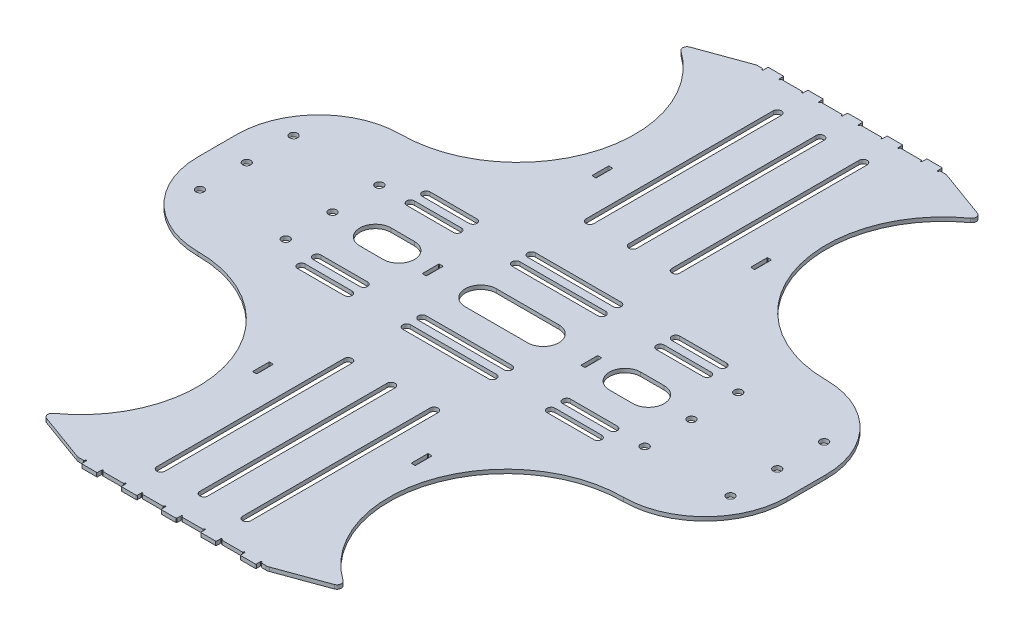
SolidWorks part; units mm, degrees
material "6061-T6 (SS)"
ref_plane "Front Plane" through (0, 0, 0) normal (0, 0, 1) x (1, 0, 0)
ref_plane "Top Plane" through (0, 0, 0) normal (0, 1, 0) x (1, 0, 0)
ref_plane "Right Plane" through (0, 0, 0) normal (1, 0, 0) x (0, 0, -1)
sketch "Sketch1" plane through (0, 0, 0) normal (0, 1, 0) x (1, 0, 0)
  line L0 (0, 0.6294) -> (0, -0.6294) construction
  line L1 (11.2708, 0) -> (-11.2708, 0) construction
  line L2 (76.108, 276.225) -> (-76.108, 276.225)
  line L3 (-78.2798, 275.842) -> (-117.0656, 261.7252)
  line L4 (-173.1053, 82.55) -> (-251.6278, 82.55) construction
  line L5 (239.7803, 15.875) -> (239.7803, -15.875)
  line L6 (78.2798, 275.842) -> (117.0656, 261.7252)
  line L7 (78.2798, -275.842) -> (117.0656, -261.7252)
  line L8 (-78.2798, -275.842) -> (-117.0656, -261.7252)
  line L9 (76.108, -276.225) -> (-76.108, -276.225)
  line L10 (-215.9, -92.7049) -> (-215.9, 92.7049) construction
  line L11 (215.9, -92.7049) -> (215.9, 92.7049) construction
  line L12 (-239.7803, 15.875) -> (-239.7803, -15.875)
  arc A0 (-76.108, 276.225) -> (-78.2798, 275.842) centre (-76.108, 269.875) ccw
  arc A1 (-117.0656, 261.7252) -> (-117.9169, 255.4325) centre (-115.8391, 258.3553) ccw
  arc A2 (-117.9169, 255.4325) -> (-173.1053, 82.55) centre (-173.1053, 177.8) cw
  arc A3 (-173.1053, 82.55) -> (-239.7803, 15.875) centre (-173.1053, 15.875) ccw
  arc A4 (173.1053, 82.55) -> (239.7803, 15.875) centre (173.1053, 15.875) cw
  arc A5 (117.9169, 255.4325) -> (173.1053, 82.55) centre (173.1053, 177.8) ccw
  arc A6 (117.0656, 261.7252) -> (117.9169, 255.4325) centre (115.8391, 258.3553) cw
  arc A7 (76.108, 276.225) -> (78.2798, 275.842) centre (76.108, 269.875) cw
  arc A8 (76.108, -276.225) -> (78.2798, -275.842) centre (76.108, -269.875) ccw
  arc A9 (117.0656, -261.7252) -> (117.9169, -255.4325) centre (115.8391, -258.3553) ccw
  arc A10 (117.9169, -255.4325) -> (173.1053, -82.55) centre (173.1053, -177.8) cw
  arc A11 (173.1053, -82.55) -> (239.7803, -15.875) centre (173.1053, -15.875) ccw
  arc A12 (-173.1053, -82.55) -> (-239.7803, -15.875) centre (-173.1053, -15.875) cw
  arc A13 (-117.9169, -255.4325) -> (-173.1053, -82.55) centre (-173.1053, -177.8) ccw
  arc A14 (-117.0656, -261.7252) -> (-117.9169, -255.4325) centre (-115.8391, -258.3553) cw
  arc A15 (-76.108, -276.225) -> (-78.2798, -275.842) centre (-76.108, -269.875) cw
  circle A16 centre (-215.9, 0) radius 3.2639
  circle A17 centre (-215.9, 38.1) radius 3.2639
  circle A18 centre (-215.9, -38.1) radius 3.2639
  circle A19 centre (215.9, -38.1) radius 3.2639
  circle A20 centre (215.9, 0) radius 3.2639
  circle A21 centre (215.9, 38.1) radius 3.2639
  circle A22 centre (-146.05, 0) radius 3.2639
  circle A23 centre (-146.05, 38.1) radius 3.2639
  circle A24 centre (-146.05, -38.1) radius 3.2639
  circle A25 centre (146.05, -38.1) radius 3.2639
  circle A26 centre (146.05, 38.1) radius 3.2639
  circle A27 centre (146.05, 0) radius 3.2639
  point P3 (77.2277, 276.225)
  point P10 (-77.2277, 276.225)
  point P17 (0, -276.225)
  point P28 (-239.7803, 0)
  point P29 (0, 276.225)
  point P50 (239.7803, 0)
  point P51 (-77.2277, -276.225)
  point P52 (77.2277, -276.225)
  dimension "D4" = 6.35
  dimension "D6" = 95.25
  dimension "D9" = 66.675
  dimension "D10" = 6.5278
  dimension "D13" = 38.1
  dimension "D2" = 20
  dimension "D3" = 41.275
  dimension "D5" = 6.35
  dimension "D7" = 276.225
  dimension "D8" = 31.75
  dimension "D11" = 76.108
  dimension "D12" = 431.8
  dimension "D15" = 69.85
  dimension "D14" = 2
base flange "Base-Flange1" sketch "Sketch1" thickness 3.175 reverse thickness direction no parameters "D1"=6.35
ref_plane "True MidPlane" through (0, -1.5875, 0) normal (0, 1, 0) x (1, 0, 0)
sketch "Sketch6" plane through (0, 0, -276.225) normal (0, 0, -1) x (-1, 0, 0)
  line L0 (-76.108, 0) -> (76.108, 0) construction
  line L1 (-6.35, 0) -> (6.35, 0)
  line L2 (-6.35, 0) -> (-6.35, -3.175)
  line L3 (-6.35, -3.175) -> (6.35, -3.175)
  line L4 (6.35, 0) -> (6.35, -3.175)
  line L5 (-6.35, 0) -> (6.35, -3.175) construction
  line L6 (-6.35, -3.175) -> (6.35, 0) construction
  line L7 (-76.108, -3.175) -> (76.108, -3.175) construction
  line L8 (25.9397, 0) -> (38.6397, 0)
  line L9 (25.9397, 0) -> (25.9397, -3.175)
  line L10 (25.9397, -3.175) -> (38.6397, -3.175)
  line L11 (38.6397, 0) -> (38.6397, -3.175)
  line L12 (25.9397, 0) -> (38.6397, -3.175) construction
  line L13 (25.9397, -3.175) -> (38.6397, 0) construction
  line L14 (58.2295, 0) -> (70.9295, 0)
  line L15 (58.2295, 0) -> (58.2295, -3.175)
  line L16 (58.2295, -3.175) -> (70.9295, -3.175)
  line L17 (70.9295, 0) -> (70.9295, -3.175)
  line L18 (58.2295, 0) -> (70.9295, -3.175) construction
  line L19 (58.2295, -3.175) -> (70.9295, 0) construction
  line L20 (0, -1.5875) -> (0, 0) construction
  line L21 (-58.2295, -3.175) -> (-70.9295, 0) construction
  line L22 (-58.2295, 0) -> (-70.9295, -3.175) construction
  line L23 (-25.9397, -3.175) -> (-38.6397, 0) construction
  line L24 (-25.9397, 0) -> (-38.6397, -3.175) construction
  line L25 (-70.9295, 0) -> (-70.9295, -3.175)
  line L26 (-58.2295, -3.175) -> (-70.9295, -3.175)
  line L27 (-58.2295, 0) -> (-58.2295, -3.175)
  line L28 (-58.2295, 0) -> (-70.9295, 0)
  line L29 (-38.6397, 0) -> (-38.6397, -3.175)
  line L30 (-25.9397, -3.175) -> (-38.6397, -3.175)
  line L31 (-25.9397, 0) -> (-25.9397, -3.175)
  line L32 (-25.9397, 0) -> (-38.6397, 0)
  point P0 (0, -1.5875)
  point P11 (32.2897, -1.5875)
  point P16 (64.5795, -1.5875)
  point P30 (-64.5795, -1.5875)
  point P31 (-32.2897, -1.5875)
  dimension "D1" = 12.7
  dimension "D3" = 32.2897
  dimension "D2" = 3
extrude "Welding Tabs" add sketch "Sketch6" along normal blind 3.175
sketch "Sketch7" plane through (0, 0, 0) normal (0, 1, 0) x (1, 0, 0)
  line L0 (-71.9455, 276.225) -> (-71.9455, 275.59)
  line L1 (-70.9295, 276.225) -> (-76.108, 276.225) construction
  line L2 (-70.9295, 276.225) -> (-70.9295, 275.59)
  line L3 (-71.9455, 276.225) -> (-70.9295, 276.225)
  line L4 (-64.5795, 279.4) -> (-64.5795, 276.225) construction
  line L5 (-70.9295, 279.4) -> (-58.2295, 279.4) construction
  line L6 (-57.2135, 276.225) -> (-58.2295, 276.225)
  line L7 (-58.2295, 276.225) -> (-58.2295, 275.59)
  line L8 (-57.2135, 276.225) -> (-57.2135, 275.59)
  line L9 (-39.6557, 276.225) -> (-39.6557, 275.59)
  line L10 (-38.6397, 276.225) -> (-38.6397, 275.59)
  line L11 (-39.6557, 276.225) -> (-38.6397, 276.225)
  line L12 (-24.9238, 276.225) -> (-25.9398, 276.225)
  line L13 (-25.9398, 276.225) -> (-25.9398, 275.59)
  line L14 (-24.9238, 276.225) -> (-24.9238, 275.59)
  line L15 (-7.366, 276.225) -> (-7.366, 275.59)
  line L16 (-6.35, 276.225) -> (-6.35, 275.59)
  line L17 (-7.366, 276.225) -> (-6.35, 276.225)
  line L18 (7.366, 276.225) -> (6.35, 276.225)
  line L19 (6.35, 276.225) -> (6.35, 275.59)
  line L20 (7.366, 276.225) -> (7.366, 275.59)
  line L21 (24.9237, 276.225) -> (24.9237, 275.59)
  line L22 (25.9397, 276.225) -> (25.9397, 275.59)
  line L23 (24.9237, 276.225) -> (25.9397, 276.225)
  line L24 (39.6557, 276.225) -> (38.6397, 276.225)
  line L25 (38.6397, 276.225) -> (38.6397, 275.59)
  line L26 (39.6557, 276.225) -> (39.6557, 275.59)
  line L27 (57.2135, 276.225) -> (57.2135, 275.59)
  line L28 (58.2295, 276.225) -> (58.2295, 275.59)
  line L29 (57.2135, 276.225) -> (58.2295, 276.225)
  line L30 (71.9455, 276.225) -> (70.9295, 276.225)
  line L31 (70.9295, 276.225) -> (70.9295, 275.59)
  line L32 (71.9455, 276.225) -> (71.9455, 275.59)
  line L33 (-38.6397, 279.4) -> (-38.6397, 276.225) construction
  line L34 (-25.9397, 279.4) -> (-25.9397, 276.225) construction
  line L37 (6.35, 279.4) -> (6.35, 276.225) construction
  line L38 (-6.35, 279.4) -> (-6.35, 276.225) construction
  arc A0 (-71.9455, 275.59) -> (-70.9295, 275.59) centre (-71.4375, 275.59) ccw
  arc A1 (-57.2135, 275.59) -> (-58.2295, 275.59) centre (-57.7215, 275.59) cw
  arc A2 (-39.6557, 275.59) -> (-38.6397, 275.59) centre (-39.1478, 275.59) ccw
  arc A3 (-24.9238, 275.59) -> (-25.9398, 275.59) centre (-25.4318, 275.59) cw
  arc A4 (-7.366, 275.59) -> (-6.35, 275.59) centre (-6.858, 275.59) ccw
  arc A5 (7.366, 275.59) -> (6.35, 275.59) centre (6.858, 275.59) cw
  arc A6 (24.9237, 275.59) -> (25.9397, 275.59) centre (25.4317, 275.59) ccw
  arc A7 (39.6557, 275.59) -> (38.6397, 275.59) centre (39.1477, 275.59) cw
  arc A8 (57.2135, 275.59) -> (58.2295, 275.59) centre (57.7215, 275.59) ccw
  arc A9 (71.9455, 275.59) -> (70.9295, 275.59) centre (71.4375, 275.59) cw
  dimension "D2" = 0.508
  dimension "D1" = 0.635
  dimension "D3" = 5
extrude "Tab Reliefs" cut sketch "Sketch7" against normal through all normal cut yes
mirror "Mirror Tabs" about plane through (0, 0, 0) normal (0, 0, 1) of "Tab Reliefs", "Welding Tabs"
fillet "Fillets for Cutter" radius 0.508 40 edges at (57.2135, -1.5875, -276.225) (71.9455, -1.5875, -276.225) (39.6557, -1.5875, -276.225) (24.9237, -1.5875, -276.225) (7.366, -1.5875, -276.225) (-7.366, -1.5875, -276.225) (-24.9238, -1.5875, -276.225) (-39.6557, -1.5875, -276.225) (-57.2135, -1.5875, -276.225) (-71.9455, -1.5875, -276.225) (57.2135, -1.5875, 276.225) (39.6557, -1.5875, 276.225) (24.9237, -1.5875, 276.225) (7.366, -1.5875, 276.225) (-7.366, -1.5875, 276.225) (-24.9238, -1.5875, 276.225) (-39.6557, -1.5875, 276.225) (-57.2135, -1.5875, 276.225) (-71.9455, -1.5875, 276.225) (70.9295, -1.5875, -279.4) (58.2295, -1.5875, -279.4) (38.6397, -1.5875, -279.4) (25.9397, -1.5875, -279.4) (6.35, -1.5875, -279.4) (-6.35, -1.5875, -279.4) (-25.9397, -1.5875, -279.4) (-38.6397, -1.5875, -279.4) (-58.2295, -1.5875, -279.4) (-70.9295, -1.5875, -279.4) (71.9455, -1.5875, 276.225) (70.9295, -1.5875, 279.4) (58.2295, -1.5875, 279.4) (38.6397, -1.5875, 279.4) (25.9397, -1.5875, 279.4) (6.35, -1.5875, 279.4) (-6.35, -1.5875, 279.4) (-25.9397, -1.5875, 279.4) (-38.6397, -1.5875, 279.4) (-58.2295, -1.5875, 279.4) (-70.9295, -1.5875, 279.4)
sketch "Sketch8" plane through (0, 0, 0) normal (0, 1, 0) x (1, 0, 0)
  line L0 (0, -78.4488) -> (0, 78.4488) construction
  line L1 (-65.7479, 6.858) -> (-63.4111, 6.858)
  line L2 (-65.7479, 144.9705) -> (-63.4111, 144.9705)
  line L3 (-66.2559, 144.4625) -> (-66.2559, 131.7625)
  line L4 (-65.7479, 131.2545) -> (-63.4111, 131.2545)
  line L5 (-62.9031, 144.4625) -> (-62.9031, 131.7625)
  line L6 (-66.2559, 144.9705) -> (-62.9031, 131.2545) construction
  line L7 (-66.2559, 131.2545) -> (-62.9031, 144.9705) construction
  line L8 (-66.2559, 6.35) -> (-66.2559, -6.35)
  line L9 (-65.7479, -6.858) -> (-63.4111, -6.858)
  line L10 (-62.9031, 6.35) -> (-62.9031, -6.35)
  line L11 (-66.2559, 6.858) -> (-62.9031, -6.858) construction
  line L12 (-66.2559, -6.858) -> (-62.9031, 6.858) construction
  line L13 (-65.7479, -131.2545) -> (-63.4111, -131.2545)
  line L14 (-66.2559, -131.7625) -> (-66.2559, -144.4625)
  line L15 (-65.7479, -144.9705) -> (-63.4111, -144.9705)
  line L16 (-62.9031, -131.7625) -> (-62.9031, -144.4625)
  line L17 (-66.2559, -131.2545) -> (-62.9031, -144.9705) construction
  line L18 (-66.2559, -144.9705) -> (-62.9031, -131.2545) construction
  line L19 (66.2559, -144.9705) -> (62.9031, -131.2545) construction
  line L20 (66.2559, -131.2545) -> (62.9031, -144.9705) construction
  line L21 (66.2559, -6.858) -> (62.9031, 6.858) construction
  line L22 (66.2559, 6.858) -> (62.9031, -6.858) construction
  line L23 (66.2559, 131.2545) -> (62.9031, 144.9705) construction
  line L24 (66.2559, 144.9705) -> (62.9031, 131.2545) construction
  line L25 (62.9031, -131.7625) -> (62.9031, -144.4625)
  line L26 (65.7479, -144.9705) -> (63.4111, -144.9705)
  line L27 (66.2559, -131.7625) -> (66.2559, -144.4625)
  line L28 (65.7479, -131.2545) -> (63.4111, -131.2545)
  line L29 (62.9031, 6.35) -> (62.9031, -6.35)
  line L30 (65.7479, -6.858) -> (63.4111, -6.858)
  line L31 (66.2559, 6.35) -> (66.2559, -6.35)
  line L32 (62.9031, 144.4625) -> (62.9031, 131.7625)
  line L33 (65.7479, 131.2545) -> (63.4111, 131.2545)
  line L34 (66.2559, 144.4625) -> (66.2559, 131.7625)
  line L35 (65.7479, 144.9705) -> (63.4111, 144.9705)
  line L36 (65.7479, 6.858) -> (63.4111, 6.858)
  arc A0 (-63.4111, 131.2545) -> (-62.9031, 131.7625) centre (-63.4111, 131.7625) ccw
  arc A1 (-66.2559, 131.7625) -> (-65.7479, 131.2545) centre (-65.7479, 131.7625) ccw
  arc A2 (-63.4111, 144.9705) -> (-62.9031, 144.4625) centre (-63.4111, 144.4625) cw
  arc A3 (-65.7479, 144.9705) -> (-66.2559, 144.4625) centre (-65.7479, 144.4625) ccw
  arc A4 (-63.4111, -6.858) -> (-62.9031, -6.35) centre (-63.4111, -6.35) ccw
  arc A5 (-66.2559, -6.35) -> (-65.7479, -6.858) centre (-65.7479, -6.35) ccw
  arc A6 (-63.4111, 6.858) -> (-62.9031, 6.35) centre (-63.4111, 6.35) cw
  arc A7 (-65.7479, 6.858) -> (-66.2559, 6.35) centre (-65.7479, 6.35) ccw
  arc A8 (-63.4111, -144.9705) -> (-62.9031, -144.4625) centre (-63.4111, -144.4625) ccw
  arc A9 (-66.2559, -144.4625) -> (-65.7479, -144.9705) centre (-65.7479, -144.4625) ccw
  arc A10 (-63.4111, -131.2545) -> (-62.9031, -131.7625) centre (-63.4111, -131.7625) cw
  arc A11 (-65.7479, -131.2545) -> (-66.2559, -131.7625) centre (-65.7479, -131.7625) ccw
  arc A12 (65.7479, -131.2545) -> (66.2559, -131.7625) centre (65.7479, -131.7625) cw
  arc A13 (63.4111, -131.2545) -> (62.9031, -131.7625) centre (63.4111, -131.7625) ccw
  arc A14 (66.2559, -144.4625) -> (65.7479, -144.9705) centre (65.7479, -144.4625) cw
  arc A15 (63.4111, -144.9705) -> (62.9031, -144.4625) centre (63.4111, -144.4625) cw
  arc A16 (65.7479, 6.858) -> (66.2559, 6.35) centre (65.7479, 6.35) cw
  arc A17 (63.4111, 6.858) -> (62.9031, 6.35) centre (63.4111, 6.35) ccw
  arc A18 (66.2559, -6.35) -> (65.7479, -6.858) centre (65.7479, -6.35) cw
  arc A19 (63.4111, -6.858) -> (62.9031, -6.35) centre (63.4111, -6.35) cw
  arc A20 (65.7479, 144.9705) -> (66.2559, 144.4625) centre (65.7479, 144.4625) cw
  arc A21 (63.4111, 144.9705) -> (62.9031, 144.4625) centre (63.4111, 144.4625) ccw
  arc A22 (66.2559, 131.7625) -> (65.7479, 131.2545) centre (65.7479, 131.7625) cw
  arc A23 (63.4111, 131.2545) -> (62.9031, 131.7625) centre (63.4111, 131.7625) cw
  point P1 (-64.5795, 138.1125)
  point P22 (-64.5795, 0)
  point P39 (-64.5795, -138.1125)
  point P102 (64.5795, -138.1125)
  point P103 (64.5795, 0)
  point P104 (64.5795, 138.1125)
  dimension "D4" = 0.508
  dimension "D1" = 64.5795
  dimension "D2" = 3.3528
  dimension "D3" = 13.716
  dimension "D5" = 138.1125
  dimension "D6" = 3
extrude "Slots for Gusset Welds" cut sketch "Sketch8" against normal through all normal cut yes
sketch "Sketch9" plane through (0, 0, 0) normal (0, 1, 0) x (1, 0, 0)
  line L0 (0, 250.825) -> (0, 98.425) construction
  line L1 (3.2639, 250.825) -> (3.2639, 98.425)
  line L2 (-3.2639, 250.825) -> (-3.2639, 98.425)
  line L3 (0, -215.3411) -> (0, -207.109) construction
  line L4 (-34.925, 250.825) -> (-34.925, 98.425) construction
  line L5 (-31.6611, 250.825) -> (-31.6611, 98.425)
  line L6 (-38.1889, 250.825) -> (-38.1889, 98.425)
  line L7 (34.925, 250.825) -> (34.925, 98.425) construction
  line L8 (31.6611, 250.825) -> (31.6611, 98.425)
  line L9 (38.1889, 250.825) -> (38.1889, 98.425)
  line L10 (-34.925, 50.8) -> (34.925, 50.8) construction
  line L11 (-7.874, 276.225) -> (-24.4158, 276.225) construction
  line L12 (189.9788, 0) -> (-189.9788, 0) construction
  line L13 (-34.925, -250.825) -> (-34.925, -98.425) construction
  line L14 (-31.6611, -250.825) -> (-31.6611, -98.425)
  line L15 (-38.1889, -250.825) -> (-38.1889, -98.425)
  line L16 (0, -250.825) -> (0, -98.425) construction
  line L17 (3.2639, -250.825) -> (3.2639, -98.425)
  line L18 (-3.2639, -250.825) -> (-3.2639, -98.425)
  line L19 (34.925, -250.825) -> (34.925, -98.425) construction
  line L20 (31.6611, -250.825) -> (31.6611, -98.425)
  line L21 (38.1889, -250.825) -> (38.1889, -98.425)
  line L22 (-34.925, 53.975) -> (34.925, 53.975)
  line L23 (-34.925, 47.625) -> (34.925, 47.625)
  line L24 (-34.925, -50.8) -> (34.925, -50.8) construction
  line L25 (-34.925, -53.975) -> (34.925, -53.975)
  line L26 (-34.925, -47.625) -> (34.925, -47.625)
  line L27 (-34.925, 38.1) -> (34.925, 38.1) construction
  line L28 (-34.925, 41.275) -> (34.925, 41.275)
  line L29 (-34.925, 34.925) -> (34.925, 34.925)
  line L30 (-34.925, -38.1) -> (34.925, -38.1) construction
  line L31 (-34.925, -41.275) -> (34.925, -41.275)
  line L32 (-34.925, -34.925) -> (34.925, -34.925)
  line L33 (-120.65, 50.8) -> (-82.55, 50.8) construction
  line L34 (-120.65, 53.975) -> (-82.55, 53.975)
  line L35 (-120.65, 47.625) -> (-82.55, 47.625)
  line L36 (-120.65, 38.1) -> (-82.55, 38.1) construction
  line L37 (-120.65, 41.275) -> (-82.55, 41.275)
  line L38 (-120.65, 34.925) -> (-82.55, 34.925)
  line L39 (120.65, 50.8) -> (82.55, 50.8) construction
  line L40 (120.65, 53.975) -> (82.55, 53.975)
  line L41 (120.65, 47.625) -> (82.55, 47.625)
  line L42 (120.65, 38.1) -> (82.55, 38.1) construction
  line L43 (120.65, 41.275) -> (82.55, 41.275)
  line L44 (120.65, 34.925) -> (82.55, 34.925)
  line L45 (-120.65, -50.8) -> (-82.55, -50.8) construction
  line L46 (-120.65, -53.975) -> (-82.55, -53.975)
  line L47 (-120.65, -47.625) -> (-82.55, -47.625)
  line L48 (-120.65, -38.1) -> (-82.55, -38.1) construction
  line L49 (-120.65, -41.275) -> (-82.55, -41.275)
  line L50 (-120.65, -34.925) -> (-82.55, -34.925)
  line L51 (120.65, -50.8) -> (82.55, -50.8) construction
  line L52 (120.65, -53.975) -> (82.55, -53.975)
  line L53 (120.65, -47.625) -> (82.55, -47.625)
  line L54 (120.65, -38.1) -> (82.55, -38.1) construction
  line L55 (120.65, -41.275) -> (82.55, -41.275)
  line L56 (120.65, -34.925) -> (82.55, -34.925)
  line L57 (-25.4, 0) -> (25.4, 0) construction
  line L58 (-25.4, 12.7) -> (25.4, 12.7)
  line L59 (-25.4, -12.7) -> (25.4, -12.7)
  line L60 (92.075, 0) -> (111.125, 0) construction
  line L61 (92.075, 12.7) -> (111.125, 12.7)
  line L62 (92.075, -12.7) -> (111.125, -12.7)
  line L63 (-92.075, 0) -> (-111.125, 0) construction
  line L64 (-92.075, 12.7) -> (-111.125, 12.7)
  line L65 (-92.075, -12.7) -> (-111.125, -12.7)
  arc A0 (3.2639, 250.825) -> (-3.2639, 250.825) centre (0, 250.825) ccw
  arc A1 (-3.2639, 98.425) -> (3.2639, 98.425) centre (0, 98.425) ccw
  arc A2 (-31.6611, 250.825) -> (-38.1889, 250.825) centre (-34.925, 250.825) ccw
  arc A3 (-38.1889, 98.425) -> (-31.6611, 98.425) centre (-34.925, 98.425) ccw
  arc A4 (31.6611, 250.825) -> (38.1889, 250.825) centre (34.925, 250.825) cw
  arc A5 (38.1889, 98.425) -> (31.6611, 98.425) centre (34.925, 98.425) cw
  arc A6 (-31.6611, -250.825) -> (-38.1889, -250.825) centre (-34.925, -250.825) cw
  arc A7 (-38.1889, -98.425) -> (-31.6611, -98.425) centre (-34.925, -98.425) cw
  arc A8 (3.2639, -250.825) -> (-3.2639, -250.825) centre (0, -250.825) cw
  arc A9 (-3.2639, -98.425) -> (3.2639, -98.425) centre (0, -98.425) cw
  arc A10 (31.6611, -250.825) -> (38.1889, -250.825) centre (34.925, -250.825) ccw
  arc A11 (38.1889, -98.425) -> (31.6611, -98.425) centre (34.925, -98.425) ccw
  arc A12 (-34.925, 53.975) -> (-34.925, 47.625) centre (-34.925, 50.8) ccw
  arc A13 (34.925, 47.625) -> (34.925, 53.975) centre (34.925, 50.8) ccw
  arc A14 (-34.925, -53.975) -> (-34.925, -47.625) centre (-34.925, -50.8) cw
  arc A15 (34.925, -47.625) -> (34.925, -53.975) centre (34.925, -50.8) cw
  arc A16 (-34.925, 41.275) -> (-34.925, 34.925) centre (-34.925, 38.1) ccw
  arc A17 (34.925, 34.925) -> (34.925, 41.275) centre (34.925, 38.1) ccw
  arc A18 (-34.925, -41.275) -> (-34.925, -34.925) centre (-34.925, -38.1) cw
  arc A19 (34.925, -34.925) -> (34.925, -41.275) centre (34.925, -38.1) cw
  arc A20 (-120.65, 53.975) -> (-120.65, 47.625) centre (-120.65, 50.8) ccw
  arc A21 (-82.55, 47.625) -> (-82.55, 53.975) centre (-82.55, 50.8) ccw
  arc A22 (-120.65, 41.275) -> (-120.65, 34.925) centre (-120.65, 38.1) ccw
  arc A23 (-82.55, 34.925) -> (-82.55, 41.275) centre (-82.55, 38.1) ccw
  arc A24 (120.65, 53.975) -> (120.65, 47.625) centre (120.65, 50.8) cw
  arc A25 (82.55, 47.625) -> (82.55, 53.975) centre (82.55, 50.8) cw
  arc A26 (120.65, 41.275) -> (120.65, 34.925) centre (120.65, 38.1) cw
  arc A27 (82.55, 34.925) -> (82.55, 41.275) centre (82.55, 38.1) cw
  arc A28 (-120.65, -53.975) -> (-120.65, -47.625) centre (-120.65, -50.8) cw
  arc A29 (-82.55, -47.625) -> (-82.55, -53.975) centre (-82.55, -50.8) cw
  arc A30 (-120.65, -41.275) -> (-120.65, -34.925) centre (-120.65, -38.1) cw
  arc A31 (-82.55, -34.925) -> (-82.55, -41.275) centre (-82.55, -38.1) cw
  arc A32 (120.65, -53.975) -> (120.65, -47.625) centre (120.65, -50.8) ccw
  arc A33 (82.55, -47.625) -> (82.55, -53.975) centre (82.55, -50.8) ccw
  arc A34 (120.65, -41.275) -> (120.65, -34.925) centre (120.65, -38.1) ccw
  arc A35 (82.55, -34.925) -> (82.55, -41.275) centre (82.55, -38.1) ccw
  arc A36 (-25.4, 12.7) -> (-25.4, -12.7) centre (-25.4, 0) ccw
  arc A37 (25.4, -12.7) -> (25.4, 12.7) centre (25.4, 0) ccw
  arc A38 (92.075, 12.7) -> (92.075, -12.7) centre (92.075, 0) ccw
  arc A39 (111.125, -12.7) -> (111.125, 12.7) centre (111.125, 0) ccw
  arc A40 (-92.075, 12.7) -> (-92.075, -12.7) centre (-92.075, 0) cw
  arc A41 (-111.125, -12.7) -> (-111.125, 12.7) centre (-111.125, 0) cw
  point P2 (0, 174.625)
  point P12 (-34.925, 174.625)
  point P19 (34.925, 174.625)
  point P25 (0, 50.8)
  point P26 (-16.1449, 276.225)
  point P34 (-34.925, -174.625)
  point P41 (0, -174.625)
  point P48 (34.925, -174.625)
  point P59 (0, -50.8)
  point P66 (0, 38.1)
  point P73 (0, -38.1)
  point P80 (-101.6, 50.8)
  point P88 (-101.6, 38.1)
  point P94 (101.6, 50.8)
  point P101 (101.6, 38.1)
  point P108 (-101.6, -50.8)
  point P115 (-101.6, -38.1)
  point P122 (101.6, -50.8)
  point P129 (101.6, -38.1)
  point P136 (0, 0)
  point P143 (101.6, 0)
  point P148 (38.1, 0)
  point P149 (38.1, 38.1)
  point P150 (123.825, 0)
  point P151 (123.825, 38.1)
  point P154 (-101.6, 0)
  dimension "D1" = 3.2639
  dimension "D5" = 3.175
  dimension "D11" = 12.7
  dimension "D12" = 12.7
  dimension "D2" = 152.4
  dimension "D3" = 34.925
  dimension "D4" = 25.4
  dimension "D6" = 50.8
  dimension "D7" = 12.7
  dimension "D8" = 38.1
  dimension "D9" = 101.6
  dimension "D10" = 2
extrude "Mounting Slots" cut sketch "Sketch9" against normal through all normal cut yes
sketch "Bend-Lines1" [suppressed] plane through (0, 0, 0) normal (0, 1, 0) x (1, 0, 0)
sketch "Bounding-Box1" [suppressed] plane through (0, 0, 0) normal (0, 1, 0) x (1, 0, 0)
sheet metal parameters "Sheet-Metal1" thickness 3.175 parameters "D1"=0.7366
flat pattern "Flat-Pattern1" [suppressed]
sketch "Bend-Lines2" plane through (0, 0, 0) normal (0, 1, 0) x (1, 0, 0)
sketch "Bounding-Box2" [suppressed] plane through (0, 0, 0) normal (0, 1, 0) x (1, 0, 0)
sheet metal parameters "Sheet-Metal2" thickness 3.175 parameters "D1"=0.7366
flat pattern "Flat-Pattern1"
sketch "Bend-Lines2" plane through (0, 0, 0) normal (0, 1, 0) x (1, 0, 0)
sketch "Bounding-Box2" [suppressed] plane through (0, 0, 0) normal (0, 1, 0) x (1, 0, 0)
sheet metal parameters "Sheet-Metal3" thickness 3.175 parameters "D1"=0.7366
flat pattern "Flat-Pattern1"
sketch "Bend-Lines2" plane through (0, 0, 0) normal (0, 1, 0) x (1, 0, 0)
sketch "Bounding-Box2" [suppressed] plane through (0, 0, 0) normal (0, 1, 0) x (1, 0, 0)
sheet metal parameters "Sheet-Metal4" thickness 3.175 parameters "D1"=0.7366
flat pattern "Flat-Pattern1"
sketch "Bend-Lines2" plane through (0, 0, 0) normal (0, 1, 0) x (1, 0, 0)
sketch3d "Bounding-Box2" [suppressed]
  line L0 (317.408, 9.525, 0) -> (317.408, -549.275, 0) construction
  line L1 (-165.192, 9.525, 0) -> (-165.192, -549.275, 0) construction
  line L2 (317.408, 9.525, 0) -> (-165.192, 9.525, 0) construction
  line L3 (317.408, -549.275, 0) -> (-165.192, -549.275, 0) construction
sheet metal parameters "Sheet-Metal5" thickness 3.175 parameters "D1"=0.7366
flat pattern "Flat-Pattern1"
sketch "Bend-Lines2" plane through (0, 0, 0) normal (0, 1, 0) x (1, 0, 0)
sketch3d "Bounding-Box2" [suppressed]
  line L0 (317.408, 9.525, 0) -> (317.408, -549.275, 0) construction
  line L1 (-165.192, 9.525, 0) -> (-165.192, -549.275, 0) construction
  line L2 (317.408, 9.525, 0) -> (-165.192, 9.525, 0) construction
  line L3 (317.408, -549.275, 0) -> (-165.192, -549.275, 0) construction
sheet metal parameters "Sheet-Metal6" thickness 3.175 parameters "D1"=0.7366
flat pattern "Flat-Pattern1"
sketch "Bend-Lines2" plane through (0, 0, 0) normal (0, 1, 0) x (1, 0, 0)
sketch3d "Bounding-Box2" [suppressed]
  line L0 (317.408, 9.525, 0) -> (317.408, -549.275, 0) construction
  line L1 (-165.192, 9.525, 0) -> (-165.192, -549.275, 0) construction
  line L2 (317.408, 9.525, 0) -> (-165.192, 9.525, 0) construction
  line L3 (317.408, -549.275, 0) -> (-165.192, -549.275, 0) construction
